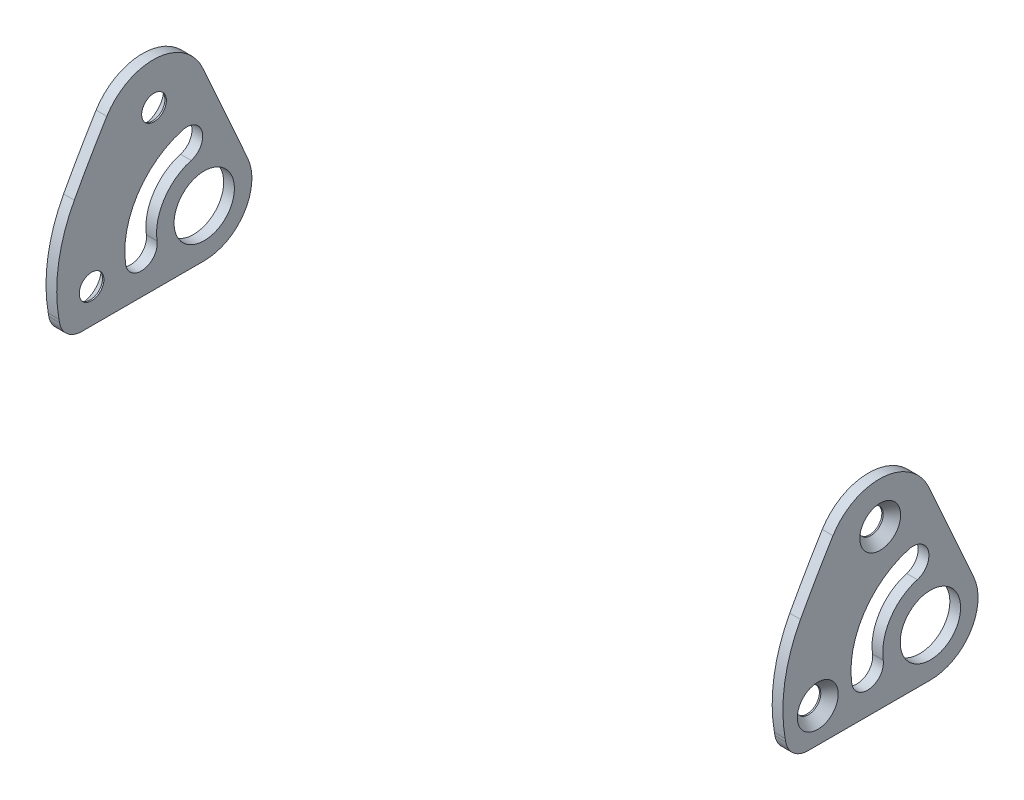
SolidWorks part; units mm, degrees
material "Ti-6Al-4VSolution treated and aged (SS)"
ref_plane "Front Plane" through (0, 0, 0) normal (0, 0, 1) x (1, 0, 0)
ref_plane "Top Plane" through (0, 0, 0) normal (0, 1, 0) x (1, 0, 0)
ref_plane "Right Plane" through (0, 0, 0) normal (1, 0, 0) x (0, 0, -1)
sketch "Sketch1" plane through (50.05, 0, 0) normal (1, 0, 0) x (0, 0, -1)
  line L1 (-163.0543, 20.32) -> (-154.0173, 20.32) construction
  line L2 (-171.2159, 20.32) -> (-151.4, 20.32)
  line L4 (-171.2159, 20.32) -> (-171.7234, 23.4009)
  line L6 (-145.3133, 29.7092) -> (-157.1514, 56.1833)
  arc A1 (-169.5759, 36.7621) -> (-157.1514, 56.1833) centre (-35.3539, -35.4198) cw
  circle A2 centre (-151.4, 26.9875) radius 4.2228
  arc A4 (-137.6934, 77.5068) -> (-169.5759, 36.7621) centre (-35.3539, -35.4198) ccw construction
  arc A6 (-171.72, -24.13) -> (-171.7234, 23.4009) centre (-306.4451, -0.3743) ccw construction
  arc A7 (-151.4, 20.32) -> (-145.3133, 29.7092) centre (-151.4, 26.9875) ccw
  arc A9 (-169.5759, 36.7621) -> (-171.7234, 23.4009) centre (-151.4, 26.9875) ccw construction
  arc A10 (-169.5759, 36.7621) -> (-171.7234, 23.4009) centre (-151.4, 26.9875) ccw
  arc A11 (-151.2839, 47.6247) -> (-153.8136, 52.6946) centre (-151.2661, 50.7996) ccw construction
  arc A12 (-151.5909, 43.748) -> (-165.0309, 44.6404) centre (-158.5471, 40.6374) ccw
  arc M26 (-171.7234, 23.4009) -> (-171.72, -24.13) centre (-306.4451, -0.3743) cw
  arc M38 (-169.5759, 36.7621) -> (-171.7234, 23.4009) centre (-151.4, 26.9875) ccw
  circle M87 centre (-152.1903, 42.519) radius 1.0922
  circle M88 centre (-161.1603, 25.0825) radius 1.0922
  dimension "D1" = 8.4455
  dimension "D2" = 7.62
extrude "Boss-Extrude1" add sketch "Sketch1" along normal blind 1.5 contours L6 A12 A1 L2 A7 A2 M38 M26 M88 M87 | M87 | M88 region at (50.05, 32.7416, 159.637) region at (50.05, 42.517, 152.1949) region at (50.05, 25.0825, 161.1603)
sketch "Sketch2" plane through (51.55, 0, 0) normal (1, 0, 0) x (0, 0, -1)
  line L4 (-161.5796, 23.495) -> (-166.5679, 23.495) construction
  line L6 (-151.637, 36.0732) -> (-154.3046, 42.0388) construction
  line L9 (-145.3133, 29.7092) -> (-151.5909, 43.748) construction
  line L10 (-171.2159, 20.32) -> (-151.4, 20.32) construction
  arc A9 (-151.4, 20.32) -> (-145.3133, 29.7092) centre (-151.4, 26.9875) ccw construction
  arc A10 (-169.5759, 36.7621) -> (-171.7234, 23.4009) centre (-151.4, 26.9875) ccw construction
  arc A12 (-153.2243, 33.4006) -> (-157.9991, 26.035) centre (-151.4, 26.9875) ccw
  arc A16 (-154.4405, 37.676) -> (-162.3985, 25.4) centre (-151.4, 26.9875) ccw
  arc A18 (-153.2243, 33.4006) -> (-154.4405, 37.676) centre (-153.8324, 35.5383) ccw
  arc A19 (-157.9991, 26.035) -> (-162.3985, 25.4) centre (-160.1988, 25.7175) cw
  dimension "D1" = 3.175
  dimension "D2" = 3.175
  dimension "D3" = 9.525
extrude "Cut-Extrude1" cut sketch "Sketch2" against normal up to next and the other way through all contours L6 A16 L4 A12 region at (51.55, 31.2483, 157.9727)
fillet "Fillet3" radius 3.175 1 edges at (50.8, 20.32, 171.2159)
sketch "Sketch3" plane through (51.55, 0, 0) normal (1, 0, 0) x (0, 0, -1)
  line L1 (-145.3133, 29.7092) -> (-151.5909, 43.748) construction
  line L2 (-168.5168, 20.32) -> (-151.4, 20.32) construction
  circle A0 centre (-167.1603, 25.0825) radius 4.7625 construction
  circle A1 centre (-158.4242, 42.4147) radius 5.8385 construction
  arc A3 (-154.4405, 37.676) -> (-162.3985, 25.4) centre (-151.4, 26.9875) ccw construction
  arc A4 (-151.5909, 43.748) -> (-165.0309, 44.6404) centre (-158.5471, 40.6374) ccw construction
  arc A5 (-169.5759, 36.7621) -> (-171.7234, 23.4009) centre (-151.4, 26.9875) ccw construction
  circle A6 centre (-158.4242, 42.4147) radius 6.7824 construction
  arc A7 (-165.0309, 44.6404) -> (-169.5759, 36.7621) centre (-35.3539, -35.4198) ccw construction
hole_wizard "CSK for #4 Flat Head Machine Screw1" positions "Sketch4" profile "Sketch6" countersink size "#4" standard "ANSI Inch" end condition up to next
sketch "Sketch4" plane through (51.55, 0, 0) normal (1, 0, 0) x (0, 0, -1)
  point P0 (-167.1603, 25.0825)
  point P3 (-158.4242, 42.4147)
sketch "Sketch6" plane through (51.55, 25.0825, 167.1603) normal (0, 1, 0) x (0, 0, -1)
  line L0 (0, 0) -> (0, 1.5)
  line L1 (0, 1.5) -> (1.7272, 1.5)
  line L2 (1.7272, 1.5) -> (1.7272, 1.3003)
  line L3 (1.7272, 1.3003) -> (2.8575, 0)
  line L5 (2.8575, 0) -> (0, 0)
  line L6 (-1.7272, 1.3003) -> (-2.8575, 0) construction
  line L11 (0, -6.35) -> (0, 107.95) construction
  dimension "Thru Hole Dia." = 3.4544
  dimension "Thru Hole Depth" = 1.5
  dimension "Near C'Sink Dia." = 5.715
  dimension "Near C'Sink Angle" = 82
mirror "Mirror2" about plane through (0, 0, 0) normal (1, 0, 0) of bodies 110 101
equation "\"weapon shaft threads\"= 5 / 16"
equation "\"D1@Sketch1\"=\"weapon shaft threads\" + .02in"
equation "\"D1@Boss-Extrude1\"=1.5mm"
